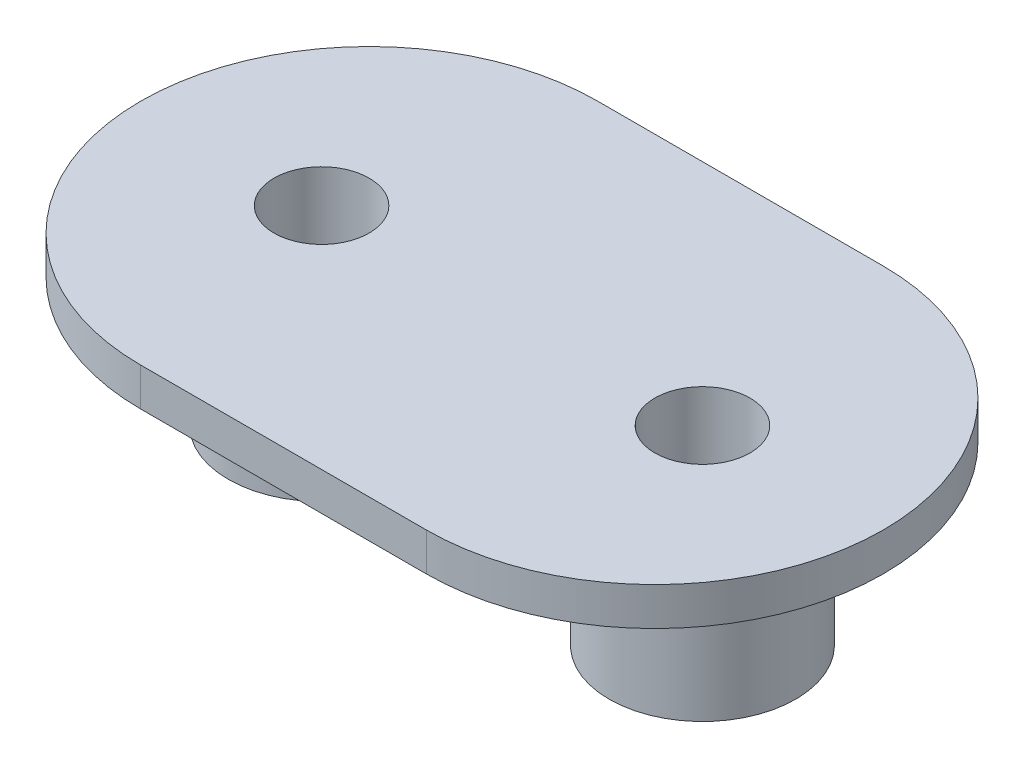
SolidWorks part; units mm, degrees
ref_plane "Front Plane" through (0, 0, 0) normal (0, 0, 1) x (1, 0, 0)
ref_plane "Top Plane" through (0, 0, 0) normal (0, 1, 0) x (1, 0, 0)
ref_plane "Right Plane" through (0, 0, 0) normal (1, 0, 0) x (0, 0, -1)
sketch "Sketch1" plane through (0, 0, 0) normal (0, 1, 0) x (1, 0, 0)
  line L0 (-10, 0) -> (10, 0) construction
  line L3 (-7.5, 12) -> (7.5, 12)
  line L4 (-7.5, -12) -> (7.5, -12)
  circle A2 centre (-10, 0) radius 4.9
  circle A3 centre (10, 0) radius 4.9
  circle A4 centre (-10, 0) radius 2.5
  circle A5 centre (10, 0) radius 2.5
  arc A6 (-7.5, 12) -> (-7.5, -12) centre (-7.5, 0) ccw
  arc A7 (7.5, 12) -> (7.5, -12) centre (7.5, 0) cw
  point P0 (0, 0)
  point P6 (0, 12)
  point P7 (0, -12)
  dimension "D2" = 9.8
  dimension "D3" = 9.8
  dimension "D5" = 5
  dimension "D6" = 5
  dimension "D1" = 20
  dimension "D4" = 15
  dimension "D7" = 10
  dimension "D8" = 15
  dimension "D9" = 10
  dimension "D10" = 24
  dimension "D11" = 12
extrude "Boss-Extrude1" add sketch "Sketch1" along normal blind 2 contours A2 A3 region at (0, 0, 0)
extrude "Boss-Extrude2" add sketch "Sketch1<3>" against normal blind 8 and the other way blind 2 separate body contours A3 A5 | A4 A2 region at (-14.7614, 0, 0) region at (5.2386, 0, 0)
sketch "Sketch1<3>" plane through (0, 0, 0) normal (0, 1, 0) x (1, 0, 0) same geometry as "Sketch1"
sketch "Sketch2" plane through (0, 2, 0) normal (0, 1, 0) x (1, 0, 0)
  circle A0 centre (-10, 0) radius 3.8861
  circle A1 centre (-10, 0) radius 5.7564
  circle A2 centre (10, 0) radius 3.8571
  circle A3 centre (10, 0) radius 6.0784
extrude "Boss-Extrude3" add sketch "Sketch2" against normal blind 2
